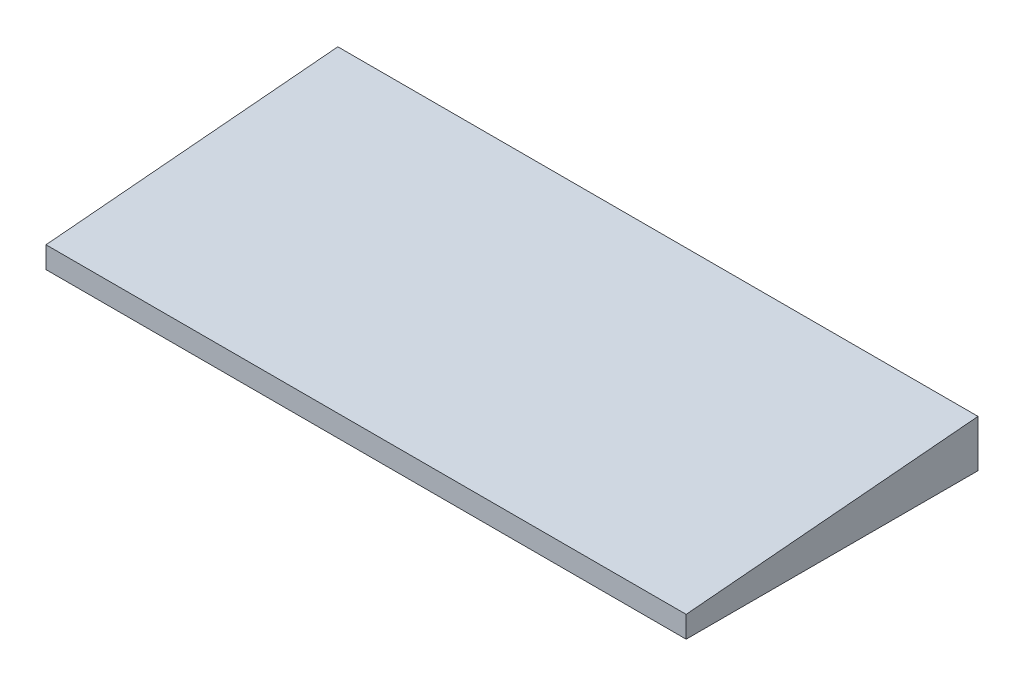
SolidWorks part; units mm, degrees
ref_plane "Front Plane" through (0, 0, 0) normal (0, 0, 1) x (1, 0, 0)
ref_plane "Top Plane" through (0, 0, 0) normal (0, 1, 0) x (1, 0, 0)
ref_plane "Right Plane" through (0, 0, 0) normal (1, 0, 0) x (0, 0, -1)
sketch "Sketch1" plane through (0, 0, 0) normal (0, 1, 0) x (1, 0, 0)
  line L1 (-170, 77.5) -> (170, 77.5)
  line L2 (-170, 77.5) -> (-170, -77.5)
  line L3 (-170, -77.5) -> (170, -77.5)
  line L4 (170, 77.5) -> (170, -77.5)
  line L5 (-170, 77.5) -> (170, -77.5) construction
  line L6 (-170, -77.5) -> (170, 77.5) construction
  point P0 (0, 0)
  dimension "D1" = 340
  dimension "D2" = 155
extrude "Boss-Extrude1" add sketch "Sketch1" along normal blind 25
sketch "Sketch2" plane through (0, 0, 0) normal (1, 0, 0) x (0, 0, -1)
  line L0 (-77.5, 11.4393) -> (77.5, 25)
  line L1 (-77.5, 25) -> (-77.5, 0) construction
  line L2 (77.5, 25) -> (-77.5, 25)
  line L3 (-77.5, 25) -> (77.5, 25) construction
  line L4 (-77.5, 25) -> (-77.5, 11.4393)
  dimension "D1" = 5
extrude "Cut-Extrude1" cut sketch "Sketch2" against normal through all both and the other way through all
